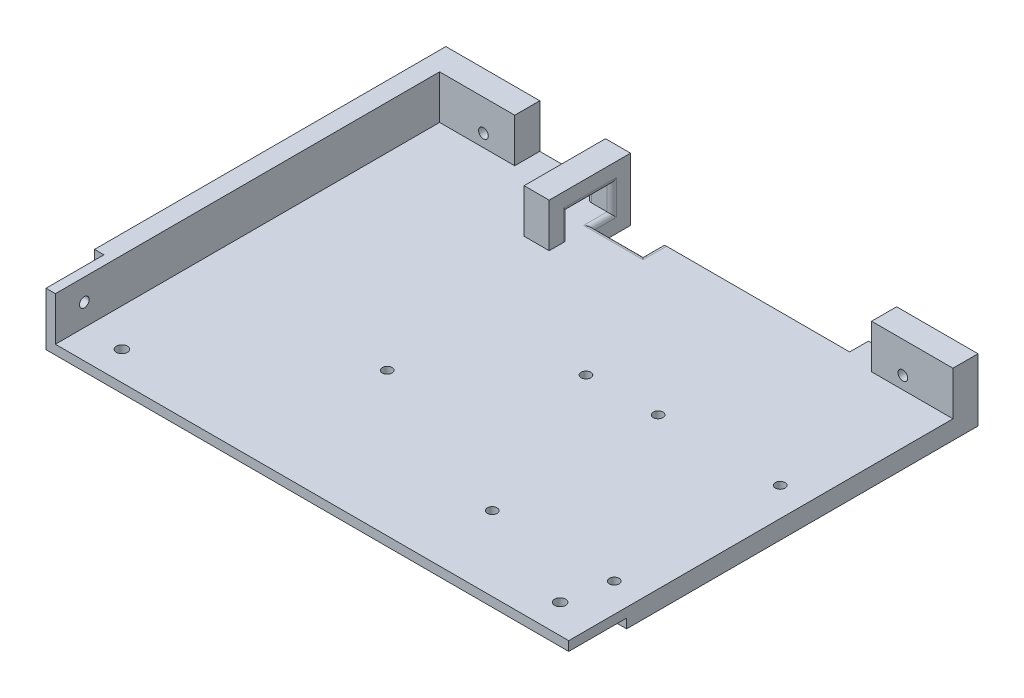
SolidWorks part; units mm, degrees
ref_plane "Front" through (0, 0, 0) normal (0, 0, 1) x (1, 0, 0)
ref_plane "Top" through (0, 0, 0) normal (0, 1, 0) x (1, 0, 0)
ref_plane "Right" through (0, 0, 0) normal (1, 0, 0) x (0, 0, -1)
sketch "Sketch1" plane through (0, 0, 0) normal (0, 1, 0) x (1, 0, 0)
  line L1 (-85, -65.375) -> (85, -65.375)
  line L2 (-85, -65.375) -> (-85, 65.375)
  line L3 (-85, 65.375) -> (85, 65.375)
  line L4 (85, -65.375) -> (85, 65.375)
  line L5 (-85, -65.375) -> (85, 65.375) construction
  line L6 (-85, 65.375) -> (85, -65.375) construction
  line L7 (-10, 65.375) -> (50, 65.375)
  line L8 (-10, 65.375) -> (-10, 59.375)
  line L9 (-10, 59.375) -> (50, 59.375)
  line L10 (50, 65.375) -> (50, 59.375)
  line L11 (-10, 65.375) -> (50, 59.375) construction
  line L12 (-10, 59.375) -> (50, 65.375) construction
  point P0 (0, 0)
  point P10 (20, 62.375)
  dimension "D1" = 130.75
  dimension "D2" = 170
  dimension "D3" = 6
  dimension "D4" = 60
  dimension "D5" = 35
extrude "Boss-Extrude1" add sketch "Sketch1" along normal blind 6 contours L3 L10 L9 L8 L2 L1 L4
sketch "Sketch2" plane through (0, 6, 0) normal (0, 1, 0) x (1, 0, 0)
  line L0 (50, 65.375) -> (85, 65.375) construction
  line L1 (-85, 65.375) -> (-55, 65.375)
  line L2 (-85, 65.375) -> (-85, 57.375)
  line L3 (-85, 57.375) -> (-55, 57.375)
  line L4 (-55, 65.375) -> (-55, 57.375)
  line L5 (-85, 65.375) -> (-55, 57.375) construction
  line L6 (-85, 57.375) -> (-55, 65.375) construction
  line L7 (85, 65.375) -> (59, 65.375)
  line L8 (85, 65.375) -> (85, 57.375)
  line L9 (85, 57.375) -> (59, 57.375)
  line L10 (59, 65.375) -> (59, 57.375)
  line L11 (85, 65.375) -> (59, 57.375) construction
  line L12 (85, 57.375) -> (59, 65.375) construction
  point P4 (-70, 61.375)
  point P10 (72, 61.375)
  dimension "D1" = 8
  dimension "D2" = 30
  dimension "D3" = 8
  dimension "D4" = 26
extrude "Boss-Extrude2" add sketch "Sketch2" along normal blind 14
sketch "Sketch3" plane through (0, 0, -57.375) normal (0, 0, 1) x (1, 0, 0)
  line L0 (-85, 20) -> (-55, 20) construction
  line L2 (-55, 20) -> (-55, 6) construction
  line L3 (59, 20) -> (85, 20) construction
  line L4 (59, 20) -> (59, 6) construction
  circle A0 centre (-65, 10) radius 1.55
  circle A1 centre (69, 10) radius 1.55
  dimension "D1" = 3.1
  dimension "D2" = 10
  dimension "D3" = 10
  dimension "D4" = 3.1
  dimension "D5" = 10
  dimension "D6" = 10
extrude "Cut-Extrude1" cut sketch "Sketch3" against normal through all
sketch "Sketch4" plane through (0, 0, 0) normal (0, 1, 0) x (1, 0, 0)
  line L0 (85, -65.375) -> (85, 57.375) construction
  line L1 (-85, -65.375) -> (85, -65.375)
  line L2 (-85, -65.375) -> (-85, -46.875)
  line L3 (-85, -46.875) -> (85, -46.875)
  line L4 (85, -65.375) -> (85, -46.875)
  line L5 (-85, -65.375) -> (85, -46.875) construction
  line L6 (-85, -46.875) -> (85, -65.375) construction
  point P4 (0, -56.125)
  dimension "D1" = 18.5
extrude "Cut-Extrude2" cut sketch "Sketch4" along normal blind 3
sketch "Sketch5" plane through (0, 3, 0) normal (0, -1, 0) x (-1, 0, 0)
  line L0 (85, -46.875) -> (85, -65.375) construction
  line L1 (-85, -65.375) -> (-85, -46.875) construction
  line L2 (85, -65.375) -> (-85, -65.375) construction
  circle A0 centre (67, -56.125) radius 1.75
  circle A1 centre (-73, -56.125) radius 1.75
  dimension "D1" = 3.5
  dimension "D2" = 3.5
  dimension "D3" = 18
  dimension "D5" = 9.25
  dimension "D4" = 12
extrude "Cut-Extrude3" cut sketch "Sketch5" against normal blind 3
sketch "Sketch7" plane through (0, 20, 0) normal (0, 1, 0) x (1, 0, 0)
  line L5 (-85, -65.375) -> (85, -65.375) construction
  line L6 (-85, 65.375) -> (-79, 65.375)
  line L12 (-85, 65.375) -> (-85, -65.375)
  line L13 (-85, -65.375) -> (-79, -65.375)
  line L15 (-79, 65.375) -> (-79, -65.375)
  line L16 (-85, 65.375) -> (-79, -65.375) construction
  line L17 (-85, -65.375) -> (-79, 65.375) construction
  line L18 (85, -46.875) -> (-85, -46.875) construction
  line L19 (-85, -65.375) -> (-82, -65.375)
  line L20 (-85, -65.375) -> (-85, -46.875)
  line L21 (-85, -46.875) -> (-82, -46.875)
  line L22 (-82, -65.375) -> (-82, -46.875)
  line L23 (-85, -65.375) -> (-82, -46.875) construction
  line L24 (-85, -46.875) -> (-82, -65.375) construction
  point P4 (-82, 0)
  point P11 (-83.5, -56.125)
  line M5 (59, 57.375) -> (85, 57.375)
  dimension "D1" = 6
  dimension "D2" = 3
extrude "Boss-Extrude3" add sketch "Sketch7" against normal up to next contours L22 L13 L12 L15 L21 M5
sketch "Sketch8" plane through (0, 6, 0) normal (0, 1, 0) x (1, 0, 0)
  line L8 (-85, -65.375) -> (-82, -65.375)
  line L9 (-82, -65.375) -> (-82, -46.875)
  line L10 (-82, -46.875) -> (-85, -46.875)
  line L11 (-85, -46.875) -> (-85, -65.375)
  line L12 (-85, -65.375) -> (-82, -65.375)
  line L13 (-82, -65.375) -> (-82, -46.875)
  line L14 (-82, -46.875) -> (-85, -46.875)
  line L15 (-85, -46.875) -> (-85, -65.375)
  dimension "D1" = 0
extrude "Cut-Extrude4" cut sketch "Sketch8" against normal up to next
sketch "Sketch9" plane through (-79, 0, 0) normal (1, 0, 0) x (0, 0, -1)
  line L1 (-65.375, 20) -> (-46.875, 20)
  line L2 (-65.375, 20) -> (-65.375, 6)
  line L3 (-65.375, 6) -> (-46.875, 6)
  line L4 (-46.875, 20) -> (-46.875, 6)
  line L5 (-65.375, 20) -> (-46.875, 6) construction
  line L6 (-65.375, 6) -> (-46.875, 20) construction
  circle A0 centre (-56.125, 13) radius 1.55
  point P4 (-56.125, 13)
  dimension "D1" = 3.1
  dimension "D2" = 14
  dimension "D3" = 18.5
extrude "Cut-Extrude5" cut sketch "Sketch9" against normal blind 10 contours A0
sketch "Sketch10" plane through (0, 6, 0) normal (0, 1, 0) x (1, 0, 0)
  line L1 (-10, 65.375) -> (-26, 65.375)
  line L2 (-10, 65.375) -> (-10, 53.375)
  line L3 (-10, 53.375) -> (-26, 53.375)
  line L4 (-26, 65.375) -> (-26, 53.375)
  line L5 (-10, 65.375) -> (-26, 53.375) construction
  line L6 (-10, 53.375) -> (-26, 65.375) construction
  point P4 (-18, 59.375)
  dimension "D1" = 12
  dimension "D2" = 16
extrude "Cut-Extrude6" cut sketch "Sketch10" against normal up to next
sketch "Sketch11" plane through (0, 6, 0) normal (0, 1, 0) x (1, 0, 0)
  line L1 (-34, 65.375) -> (-26, 65.375)
  line L2 (-34, 65.375) -> (-34, 39.375)
  line L3 (-34, 39.375) -> (-26, 39.375)
  line L4 (-26, 65.375) -> (-26, 39.375)
  line L5 (-34, 65.375) -> (-26, 39.375) construction
  line L6 (-34, 39.375) -> (-26, 65.375) construction
  point P4 (-30, 52.375)
  dimension "D1" = 26
  dimension "D2" = 8
extrude "Boss-Extrude4" add sketch "Sketch11" along normal blind 14
sketch "Sketch13" plane through (-26, 0, 0) normal (1, 0, 0) x (0, 0, -1)
  line L4 (45.375, 12) -> (45.375, 6)
  line L5 (39.375, 6) -> (53.375, 6) construction
  line L6 (45.375, 6) -> (59.375, 6)
  line L7 (59.375, 6) -> (59.375, 12)
  line L8 (45.375, 12) -> (59.375, 12)
  line L9 (59.375, 12) -> (59.375, 14)
  line L10 (59.375, 14) -> (45.375, 14)
  line L11 (45.375, 14) -> (45.375, 12)
  line L13 (59.375, 12) -> (59.375, 14)
  line L14 (59.375, 14) -> (45.375, 14)
  line L15 (45.375, 14) -> (45.375, 12)
  dimension "D1" = 6
extrude "Cut-Extrude7" cut sketch "Sketch13" against normal up to next
fillet "Fillet1" radius 1.5 9 edges at (-34, 10, -59.375) (-26, 10, -59.375) (-34, 14, -52.375) (-34, 10, -45.375) (-26, 14, -52.375) (-26, 10, -45.375) (-10, 6, -56.375) (-26, 6, -56.375) (-18, 6, -53.375)
sketch "Sketch15" plane through (0, 6, 0) normal (0, 1, 0) x (1, 0, 0)
  line L0 (-79, -65.375) -> (-79, 57.375) construction
  line L1 (-60.9433, -85.645) -> (19.0567, -85.645) construction
  line L2 (-60.9433, -85.645) -> (-60.9433, 14.355) construction
  line L3 (-60.9433, 14.355) -> (19.0567, 14.355) construction
  line L4 (19.0567, -85.645) -> (19.0567, 14.355) construction
  line L5 (-60.9433, -85.645) -> (19.0567, 14.355) construction
  line L6 (-60.9433, 14.355) -> (19.0567, -85.645) construction
  line L7 (-36.54, -85.645) -> (16.8, -85.645)
  line L8 (-36.54, -85.645) -> (-36.54, 14.355)
  line L9 (-36.54, 14.355) -> (16.8, 14.355)
  line L10 (16.8, -85.645) -> (16.8, 14.355)
  line L11 (-36.54, -85.645) -> (16.8, 14.355) construction
  line L12 (-36.54, 14.355) -> (16.8, -85.645) construction
  line L13 (-79, -65.375) -> (85, -65.375) construction
  line L14 (59, 57.375) -> (85, 57.375) construction
  line L15 (29.5953, 19.6881) -> (81.5953, 19.6881) construction
  line L16 (29.5953, 19.6881) -> (29.5953, -40.3119) construction
  line L17 (29.5953, -40.3119) -> (81.5953, -40.3119) construction
  line L18 (81.5953, 19.6881) -> (81.5953, -40.3119) construction
  line L19 (29.5953, 19.6881) -> (81.5953, -40.3119) construction
  line L20 (29.5953, -40.3119) -> (81.5953, 19.6881) construction
  circle A0 centre (14.26, -71.675) radius 1.55
  circle A1 centre (14.26, 10.875) radius 1.55
  circle A2 centre (-34, -70.375) radius 1.55
  circle A3 centre (-18.8, -19.575) radius 1.55
  circle A4 centre (36.8, 11.375) radius 1.55
  circle A5 centre (75.8, 11.375) radius 1.55
  circle A6 centre (75.8, -41.625) radius 1.55
  circle A7 centre (36.8, -41.625) radius 1.55
  point P0 (-20.9433, -35.645)
  point P6 (-9.87, -35.645)
  point P26 (55.5953, -10.3119)
  dimension "D5" = 3.1
  dimension "D7" = 2.54
  dimension "D8" = 3.1
  dimension "D10" = 3.1
  dimension "D11" = 48.26
  dimension "D12" = 1.3
  dimension "D13" = 3.1
  dimension "D14" = 50.8
  dimension "D15" = 15.2
  dimension "D16" = 45
  dimension "D17" = 5
  dimension "D20" = 3.1
  dimension "D23" = 46
  dimension "D1" = 100
  dimension "D2" = 80
  dimension "D3" = 100
  dimension "D4" = 53.34
  dimension "D6" = 13.97
  dimension "D9" = 82.55
  dimension "D18" = 60
  dimension "D19" = 52
  dimension "D24" = 20
  dimension "D21" = 2
  dimension "D22" = 2
extrude "Cut-Extrude8" cut sketch "Sketch15" against normal up to next contours A3 | A1 | A4 | A5 | A6 | A7
